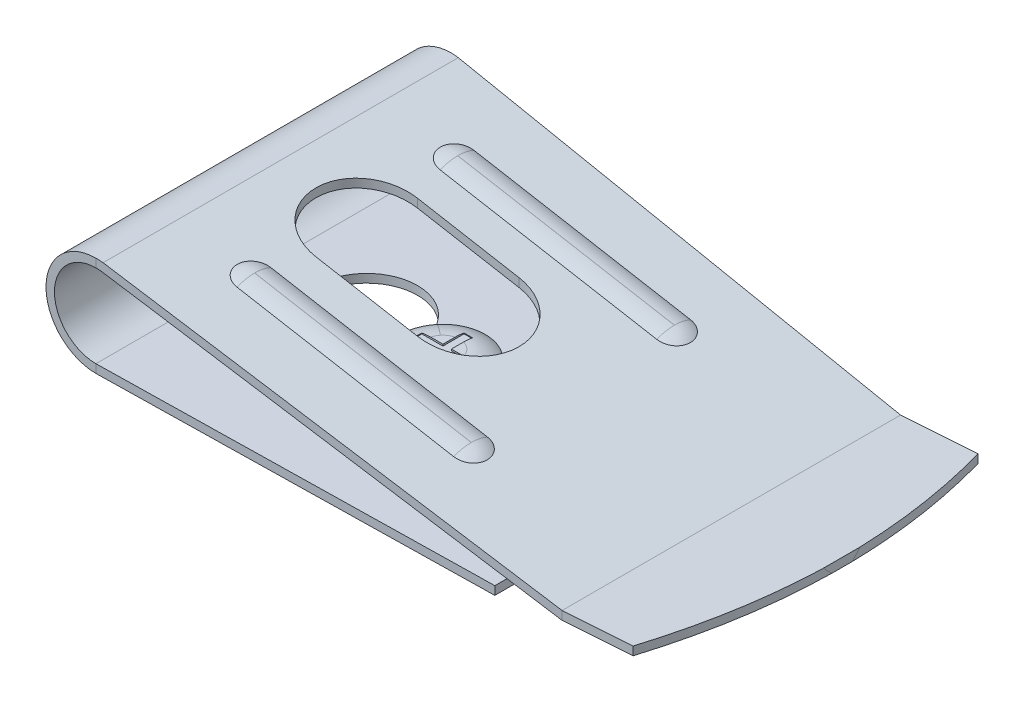
SolidWorks part; units mm, degrees
ref_plane "Front Plane" through (0, 0, 0) normal (0, 0, 1) x (1, 0, 0)
ref_plane "Top Plane" through (0, 0, 0) normal (0, 1, 0) x (1, 0, 0)
ref_plane "Right Plane" through (0, 0, 0) normal (1, 0, 0) x (0, 0, -1)
sketch "Sketch1" plane through (0, 0, 0) normal (0, 0, 1) x (1, 0, 0)
  line L0 (0.0126, -0.5003) -> (-5.9746, -0.8933)
  line L1 (0, 0) -> (0.0126, -0.5003)
  line L2 (-5.9746, -0.8933) -> (-32.6505, 3.8425)
  line L3 (0, 0) -> (-5.9468, -0.3904)
  line L4 (-32.9874, -1.0342) -> (0.0126, -1.0342)
  line L5 (0.0126, -1.0342) -> (0.0126, -1.5342)
  line L6 (-5.9468, -0.3904) -> (-32.572, 4.3364)
  line L7 (-32.9874, -1.5342) -> (0.0126, -1.5342)
  line L8 (-0.0202, -0.0013) -> (-5.9468, -0.3904) construction
  arc A0 (-32.6505, 3.8425) -> (-32.9874, -1.0342) centre (-32.9874, 1.4158) ccw
  arc A1 (-32.572, 4.3364) -> (-32.9874, -1.5342) centre (-32.9874, 1.4158) ccw
  dimension "D1" = 2.45
  dimension "D2" = 33
  dimension "D3" = 6
  dimension "D4" = 0.5
extrude "Boss-Extrude1" add sketch "Sketch1" along normal blind 21
sketch "Sketch2" plane through (0, -1.5342, 0) normal (0, -1, 0) x (1, 0, 0)
  line L0 (-32.9874, 21) -> (-5.9468, 20.5)
  line L1 (-5.9468, 20.5) -> (-1.7551, 20.5)
  line L2 (0.0126, 21) -> (0.0126, 0) construction
  line L3 (-35.9374, 10.5) -> (0.0126, 10.5) construction
  line L4 (-35.9374, 21) -> (-35.9374, 0) construction
  line L6 (-32.9874, 21) -> (-32.9874, 0) construction
  line L8 (-32.9874, 0) -> (0.0126, 0) construction
  line L9 (-5.9468, 0.5) -> (-32.9874, 0)
  line L10 (-5.9468, 0.5) -> (-1.3723, 0.5)
  line L11 (-32.9874, 21) -> (0.0126, 21)
  line L12 (0.0126, 21) -> (0.0126, 10.5)
  line L13 (-32.9874, 0) -> (0, 0)
  line L14 (0, 0) -> (0.7861, 0)
  line L15 (0.7861, 0) -> (0.0126, 10.5)
  spline S0 degree 2 poles (-1.7551, 20.5) (1.5877, 10.5588) (-1.3723, 0.5) knots 0 0 0 1 1 1
  line M1 (-32.9874, 0) -> (0.0126, 0)
  line M2 (0.0126, 0) -> (0.0126, 21)
  line M3 (0.0126, 21) -> (-32.9874, 21)
  dimension "D1" = 0.5
  dimension "D2" = 0.5
  dimension "D3" = 27.0406
  dimension "D4" = 27.0406
extrude "Cut-Extrude1" cut sketch "Sketch2" against normal blind 21 contours S0 L10 L9 M1 | L1 S0 L0 M2 M3 region at (-16.4874, -1.5342, 20.9654) region at (-0.3304, -1.5342, 4.672)
sketch "Sketch3" plane through (0, -1.5342, 0) normal (0, -1, 0) x (1, 0, 0)
  line L1 (0.1532, 21.1319) -> (-9.8468, 21.1319)
  line L2 (0.1532, 21.1319) -> (0.1532, -2.3461)
  line L3 (0.1532, -2.3461) -> (-9.8468, -2.3461)
  line L4 (-9.8468, 21.1319) -> (-9.8468, -2.3461)
  dimension "D1" = 10
extrude "Cut-Extrude2" cut sketch "Sketch3" against normal blind 0.5
sketch "Sketch4" plane through (0, -1.5342, 0) normal (0, -1, 0) x (1, 0, 0)
  line L0 (-35.9374, 10.5) -> (0.0126, 10.5) construction
  line L1 (-35.9374, 21) -> (-35.9374, 0) construction
  line L2 (-27.4874, 20.8983) -> (-27.4874, 0.1017) construction
  line L5 (-32.9874, 21) -> (-9.8468, 20.5721) construction
  line L6 (-9.8468, 0.4279) -> (-32.9874, 0) construction
  line L7 (-32.9874, 21) -> (-32.9874, 0) construction
  line L8 (-22.9874, 12) -> (-24.8894, 12)
  line L9 (-22.9874, 9) -> (-24.8894, 9)
  arc A0 (-24.8894, 12) -> (-24.8894, 9) centre (-27.4874, 10.5) ccw
  arc A1 (-22.9874, 9) -> (-22.9874, 12) centre (-22.9874, 10.5) ccw
  dimension "D2" = 6
  dimension "D3" = 3
  dimension "D1" = 5.5
extrude "Cut-Extrude3" cut sketch "Sketch4" against normal blind 0.5
sketch "Sketch5" plane through (0, -1.0342, 0) normal (0, 1, 0) x (1, 0, 0)
  line L0 (-27.4874, -13.5) -> (-21.4874, -13.5)
  line L1 (-27.4874, -7.5) -> (-21.4874, -7.5)
  arc A0 (-27.4874, -7.5) -> (-27.4874, -13.5) centre (-27.4874, -10.5) ccw
  arc A1 (-21.4874, -13.5) -> (-21.4874, -7.5) centre (-21.4874, -10.5) ccw
  arc A2 (-22.9874, -12) -> (-22.9874, -9) centre (-22.9874, -10.5) ccw construction
  dimension "D1" = 6
  dimension "D2" = 6
extrude "Cut-Extrude4" cut sketch "Sketch5" along normal blind 11.5
sketch "Sketch6" plane through (-0.2489, -1.402, 0) normal (0.1748, 0.9846, 0) x (0.9846, -0.1748, 0)
  line L0 (-21.5706, -7.5) -> (-27.6645, -7.5) construction
  line L1 (-28.3391, -3.5) -> (-15.3391, -3.5)
  line L3 (-28.3391, -5.5) -> (-15.3391, -5.5)
  line L5 (-28.3391, -15.5) -> (-15.3391, -15.5)
  line L7 (-28.3391, -17.5) -> (-15.3391, -17.5)
  line L9 (-27.6645, -13.5) -> (-21.5706, -13.5) construction
  arc A0 (-28.3391, -3.5) -> (-28.3391, -5.5) centre (-28.3391, -4.5) ccw
  arc A1 (-15.3391, -5.5) -> (-15.3391, -3.5) centre (-15.3391, -4.5) ccw
  arc A2 (-15.3391, -17.5) -> (-15.3391, -15.5) centre (-15.3391, -16.5) ccw
  arc A3 (-28.3391, -15.5) -> (-28.3391, -17.5) centre (-28.3391, -16.5) ccw
  dimension "D1" = 2
  dimension "D2" = 2
  dimension "D3" = 2
  dimension "D4" = 2
  dimension "D5" = 13
  dimension "D6" = 13
  dimension "D7" = 13
  dimension "D8" = 13
extrude "Boss-Extrude2" add sketch "Sketch6" along normal blind 0.25
fillet "Fillet1" radius 2.1 4 edges at (-21.7081, 2.6616, 3.5) (-21.7081, 2.6616, 5.5) (-21.7081, 2.6616, 15.5) (-21.7081, 2.6616, 17.5)
sketch "Sketch7" plane through (0, -1.0342, 0) normal (0, 1, 0) x (1, 0, 0)
  circle A0 centre (-22.9874, -10.5) radius 2.5
  dimension "D1" = 5
extrude "Boss-Extrude3" add sketch "Sketch7" along normal blind 0.5
sketch "Sketch8" plane through (0, -0.5342, 0) normal (0, 1, 0) x (1, 0, 0)
  line L0 (-22.9874, -8) -> (-22.9874, -13) construction
  line L1 (-23.2374, -9) -> (-22.7374, -9)
  line L2 (-23.2374, -9) -> (-23.2374, -12)
  line L3 (-23.2374, -12) -> (-22.7374, -12)
  line L4 (-22.7374, -9) -> (-22.7374, -12)
  line L5 (-24.4874, -10.25) -> (-21.4874, -10.25)
  line L6 (-24.4874, -10.25) -> (-24.4874, -10.75)
  line L7 (-24.4874, -10.75) -> (-21.4874, -10.75)
  line L8 (-21.4874, -10.25) -> (-21.4874, -10.75)
  line L9 (-25.4874, -10.5) -> (-20.4874, -10.5) construction
  circle A0 centre (-22.9874, -10.5) radius 2.5 construction
  dimension "D1" = 3
  dimension "D2" = 3
  dimension "D3" = 0.5
  dimension "D4" = 0.5
  dimension "D5" = 1.5
  dimension "D6" = 0.25
  dimension "D7" = 0.25
  dimension "D8" = 1.5
extrude "Cut-Extrude5" cut sketch "Sketch8" against normal blind 0.1 contours L7 L2 L3 L4 | L2 L7 L4 L5 | L2 L5 L4 L1 | L6 L7 L2 L5 | L8 L5 L4 L7 region at (-22.9874, -0.5342, 9.625) region at (-22.9874, -0.5342, 10.5) region at (-23.8624, -0.5342, 10.5) region at (-22.1124, -0.5342, 10.5) region at (-22.9874, -0.5342, 11.375)
fillet "Fillet2" radius 2.49 1 edges at (-25.4874, -0.5342, 10.5)
